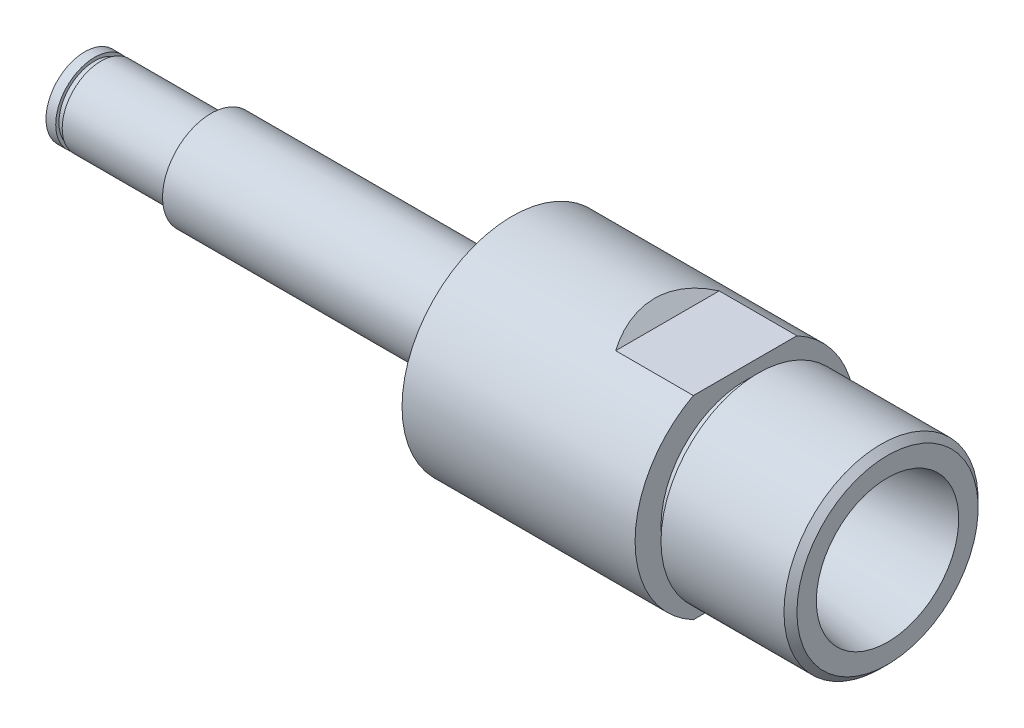
SolidWorks part; units mm, degrees
ref_plane "前视基准面" through (0, 0, 0) normal (0, 0, 1) x (1, 0, 0)
ref_plane "上视基准面" through (0, 0, 0) normal (0, 1, 0) x (1, 0, 0)
ref_plane "右视基准面" through (0, 0, 0) normal (1, 0, 0) x (0, 0, -1)
other "Configuration Table"
sketch "草图1" plane through (0, 0, 0) normal (0, 0, 1) x (1, 0, 0)
  line L0 (-14.7148, 0) -> (32.2438, 0) construction
  line L1 (0, 6.5) -> (0, 17)
  line L2 (0, 17) -> (36, 17)
  line L3 (36, 17) -> (36, 13)
  line L4 (36, 13) -> (38, 13)
  line L5 (38, 13) -> (38, 15)
  line L6 (38, 15) -> (58, 15)
  line L7 (58, 15) -> (58, 11)
  line L8 (58, 11) -> (42, 8.6801)
  line L9 (42, 8.6801) -> (42, 9.5)
  line L10 (42, 9.5) -> (37, 9.5)
  line L11 (37, 9.5) -> (37, 9)
  line L12 (37, 9) -> (31, 9)
  line L13 (31, 9) -> (31, 9.5)
  line L14 (31, 9.5) -> (26, 9.5)
  line L15 (26, 9.5) -> (26, 7)
  line L16 (26, 7) -> (10, 7)
  line L17 (10, 7) -> (5.794, 0)
  line L18 (0, 6.5) -> (-2, 6.5)
  line L19 (-2, 6.5) -> (-2, 7.5)
  line L20 (-2, 7.5) -> (-46.5, 7.5)
  line L21 (-46.5, 7.5) -> (-46.5, 5.5)
  line L22 (-46.5, 5.5) -> (-47.5, 5.5)
  line L23 (-47.5, 5.5) -> (-47.5, 6)
  line L24 (-47.5, 6) -> (-63.5, 6)
  line L25 (-63.5, 6) -> (-63.5, 5.5)
  line L26 (-63.5, 5.5) -> (-64.5, 5.5)
  line L27 (-64.5, 5.5) -> (-64.5, 6)
  line L28 (-64.5, 6) -> (-66, 6)
  line L29 (-66, 6) -> (-66, 0)
  line L30 (5.794, 0) -> (-66, 0)
  point P24 (24.4017, 8.7806)
  point P34 (-52.0862, 6)
  point P35 (-61.7477, 6)
  point P36 (-14.0754, -8.6718)
  point P37 (-14.0754, -8.7691)
  dimension "D1" = 6
  dimension "D2" = 6
  dimension "D3" = 7.5
  dimension "D4" = 6.5
  dimension "D5" = 2
  dimension "D6" = 1
  dimension "D7" = 5.5
  dimension "D8" = 5.5
  dimension "D9" = 1
  dimension "D10" = 17
  dimension "D11" = 15
  dimension "D12" = 13
  dimension "D13" = 2
  dimension "D14" = 7
  dimension "D15" = 9.5
  dimension "D16" = 9.5
  dimension "D17" = 9
  dimension "D18" = 5
  dimension "D19" = 6
  dimension "D20" = 5
  dimension "D21" = 124
  dimension "D22" = 58
  dimension "D23" = 46.5
  dimension "D24" = 16
  dimension "D25" = 59
  dimension "D26" = 32
  dimension "D27" = 8.25
  dimension "D28" = 22
  dimension "D29" = 22
  dimension "D30" = 48
revolve "旋转1" add sketch "草图1" angle 360 about L0
sketch "草图4" plane through (36, 0, 0) normal (1, 0, 0) x (0, 0, -1)
  line L1 (-8, -15) -> (8, -15)
  line L3 (-8, 15) -> (8, 15)
  line L5 (-14.4376, -8.9753) -> (14.4376, 8.9753) construction
  line L6 (-14.4376, 8.9753) -> (14.4376, -8.9753) construction
  arc A0 (-8, 15) -> (-8, -15) centre (0, 0) ccw
  arc A1 (8, -15) -> (8, 15) centre (0, 0) ccw
  dimension "D1" = 34
extrude "切除-拉伸2" cut sketch "草图4" against normal blind 14 flip side to cut
chamfer "倒角1" distance 2 angle 45 2 edges at (22, -15, 0) (22, 15, 0)
chamfer "倒角2" distance 1 angle 45 1 edges at (58, 0, 15)
